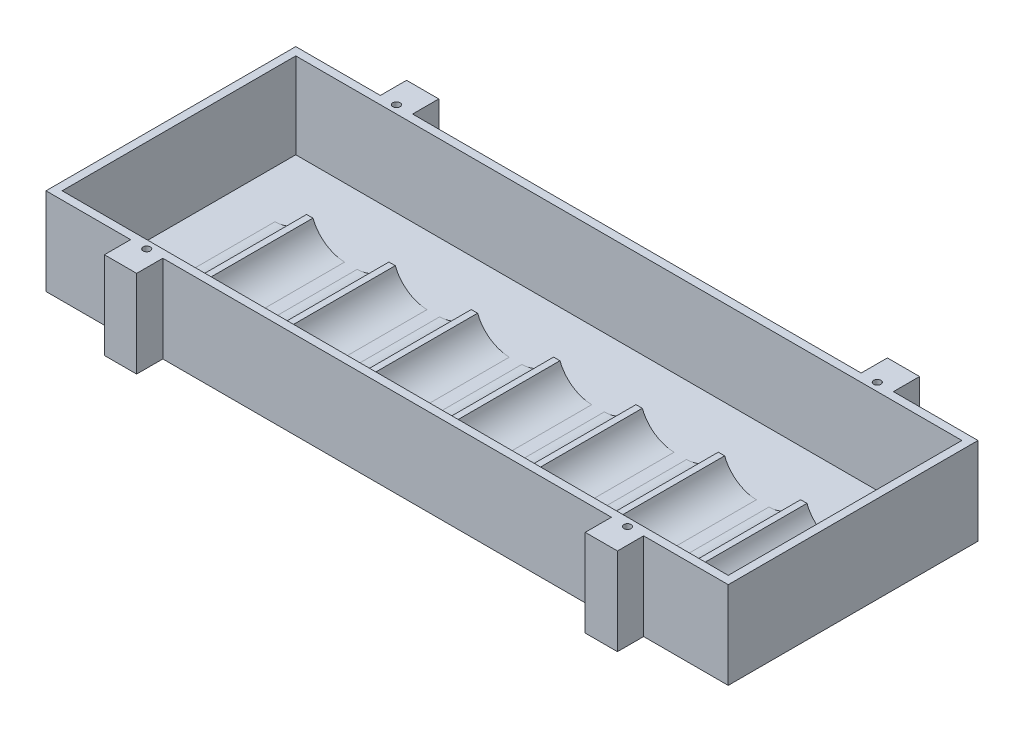
SolidWorks part; units mm, degrees
material "ABS"
ref_plane "Front Plane" through (0, 0, 0) normal (0, 0, 1) x (1, 0, 0)
ref_plane "Top Plane" through (0, 0, 0) normal (0, 1, 0) x (1, 0, 0)
ref_plane "Right Plane" through (0, 0, 0) normal (1, 0, 0) x (0, 0, -1)
sketch "Sketch1" plane through (0, 0, 0) normal (0, 1, 0) x (1, 0, 0)
  line L0 (2.54, -2.54) -> (2.54, -76.2)
  line L1 (0, 0) -> (215.08, 0)
  line L2 (0, 0) -> (0, -78.74)
  line L3 (0, -78.74) -> (215.08, -78.74)
  line L4 (215.08, 0) -> (215.08, -78.74)
  line L5 (2.54, -76.2) -> (212.54, -76.2)
  line L6 (212.54, -2.54) -> (212.54, -76.2)
  line L7 (2.54, -2.54) -> (212.54, -2.54)
  line L8 (0, 0) -> (0, 8.255)
  line L9 (0, 8.255) -> (215.08, 8.255)
  line L10 (215.08, 8.255) -> (215.08, 0)
  line L11 (0, -78.74) -> (0, -86.995)
  line L12 (0, -86.995) -> (215.08, -86.995)
  line L13 (215.08, -86.995) -> (215.08, -78.74)
  dimension "D1" = 73.66
  dimension "D2" = 210
  dimension "D4" = 10.795
  dimension "D5" = 95.25
  dimension "D3" = 2.54
extrude "Boss-Extrude1" add sketch "Sketch1" against normal blind 0.508 contours L2 L3 L4 L1
extrude "Boss-Extrude2" add sketch "Sketch1<3>" along normal blind 27 contours L10 L9 L8 L1 | L12 L13 L3 L11 | L4 L1 L2 L3 L0 L7 L6 L5 region at (107.54, 0, -4.1275) region at (107.54, 0, 2.2904) region at (107.54, 0, 82.8675)
sketch "Sketch1<3>" plane through (0, 0, 0) normal (0, 1, 0) x (1, 0, 0) same geometry as "Sketch1"
sketch "Sketch2" plane through (0, 0, 0) normal (0, 1, 0) x (-1, 0, 0)
  line L0 (-28.54, 0) -> (-28.54, 78.74) construction
  line L1 (-2.54, 2.54) -> (-2.54, 76.2) construction
  line L2 (-17.54, 0) -> (-17.54, 78.74) construction
  line L9 (0, 0) -> (-215.08, 0) construction
  line L10 (0, 78.74) -> (-215.08, 78.74) construction
  dimension "D1" = 26
  dimension "D2" = 15
sketch "Sketch5" plane through (0, 0, 2.54) normal (0, 0, 1) x (1, 0, 0)
  line L0 (28.54, 0) -> (28.54, 7) construction
  line L1 (29.54, 7) -> (27.54, 7)
  line L2 (0, 0) -> (215.08, 0) construction
  line L3 (17.54, 0) -> (39.54, 0)
  line L4 (55.4988, 7) -> (53.4988, 7)
  line L5 (43.4988, 0) -> (65.4988, 0)
  line L6 (54.4988, 0) -> (54.4988, 7) construction
  line L7 (81.4576, 7) -> (79.4576, 7)
  line L8 (69.4576, 0) -> (91.4576, 0)
  line L9 (80.4576, 0) -> (80.4576, 7) construction
  line L10 (107.4164, 7) -> (105.4164, 7)
  line L11 (95.4164, 0) -> (117.4164, 0)
  line L12 (106.4164, 0) -> (106.4164, 7) construction
  line L13 (133.3752, 7) -> (131.3752, 7)
  line L14 (121.3752, 0) -> (143.3752, 0)
  line L15 (132.3752, 0) -> (132.3752, 7) construction
  line L31 (159.334, 7) -> (157.334, 7)
  line L32 (147.334, 0) -> (169.334, 0)
  line L33 (158.334, 0) -> (158.334, 7) construction
  line L34 (185.2928, 7) -> (183.2928, 7)
  line L35 (173.2928, 0) -> (195.2928, 0)
  line L36 (184.2928, 0) -> (184.2928, 7) construction
  line L37 (170.06, 7) -> (168.06, 7) [skipped]
  line L38 (158.06, 0) -> (180.06, 0) [skipped]
  line L39 (169.06, 0) -> (169.06, 7) construction
  line L40 (145.64, 0) -> (145.64, 7) construction
  line L41 (134.64, 0) -> (156.64, 0) [skipped]
  line L42 (146.64, 7) -> (144.64, 7) [skipped]
  line L43 (122.22, 0) -> (122.22, 7) construction
  line L44 (111.22, 0) -> (133.22, 0) [skipped]
  line L45 (123.22, 7) -> (121.22, 7) [skipped]
  line L46 (98.8, 0) -> (98.8, 7) construction
  line L47 (87.8, 0) -> (109.8, 0) [skipped]
  line L48 (99.8, 7) -> (97.8, 7) [skipped]
  line L49 (75.38, 0) -> (75.38, 7) construction
  line L50 (64.38, 0) -> (86.38, 0) [skipped]
  line L51 (76.38, 7) -> (74.38, 7) [skipped]
  line L52 (51.96, 0) -> (51.96, 7) construction
  line L53 (40.96, 0) -> (62.96, 0) [skipped]
  line L54 (52.96, 7) -> (50.96, 7) [skipped]
  arc A0 (17.54, 0) -> (27.54, 7) centre (17.292, 10.9972) ccw
  arc A1 (39.54, 0) -> (29.54, 7) centre (39.788, 10.9972) cw
  arc A2 (65.4988, 0) -> (55.4988, 7) centre (65.7468, 10.9972) cw
  arc A3 (43.4988, 0) -> (53.4988, 7) centre (43.2508, 10.9972) ccw
  arc A4 (91.4576, 0) -> (81.4576, 7) centre (91.7056, 10.9972) cw
  arc A5 (69.4576, 0) -> (79.4576, 7) centre (69.2096, 10.9972) ccw
  arc A6 (117.4164, 0) -> (107.4164, 7) centre (117.6644, 10.9972) cw
  arc A7 (95.4164, 0) -> (105.4164, 7) centre (95.1684, 10.9972) ccw
  arc A8 (143.3752, 0) -> (133.3752, 7) centre (143.6232, 10.9972) cw
  arc A9 (121.3752, 0) -> (131.3752, 7) centre (121.1272, 10.9972) ccw
  arc A20 (169.334, 0) -> (159.334, 7) centre (169.582, 10.9972) cw
  arc A21 (147.334, 0) -> (157.334, 7) centre (147.086, 10.9972) ccw
  arc A22 (195.2928, 0) -> (185.2928, 7) centre (195.5408, 10.9972) cw
  arc A23 (173.2928, 0) -> (183.2928, 7) centre (173.0448, 10.9972) ccw
  arc A24 (180.06, 0) -> (170.06, 7) centre (180.308, 10.9972) cw [skipped]
  arc A25 (158.06, 0) -> (168.06, 7) centre (157.812, 10.9972) ccw [skipped]
  arc A26 (134.64, 0) -> (144.64, 7) centre (134.392, 10.9972) ccw [skipped]
  arc A27 (156.64, 0) -> (146.64, 7) centre (156.888, 10.9972) cw [skipped]
  arc A28 (111.22, 0) -> (121.22, 7) centre (110.972, 10.9972) ccw [skipped]
  arc A29 (133.22, 0) -> (123.22, 7) centre (133.468, 10.9972) cw [skipped]
  arc A30 (87.8, 0) -> (97.8, 7) centre (87.552, 10.9972) ccw [skipped]
  arc A31 (109.8, 0) -> (99.8, 7) centre (110.048, 10.9972) cw [skipped]
  arc A32 (64.38, 0) -> (74.38, 7) centre (64.132, 10.9972) ccw [skipped]
  arc A33 (86.38, 0) -> (76.38, 7) centre (86.628, 10.9972) cw [skipped]
  arc A34 (62.96, 0) -> (52.96, 7) centre (63.208, 10.9972) cw [skipped]
  arc A35 (40.96, 0) -> (50.96, 7) centre (40.712, 10.9972) ccw [skipped]
  dimension "D2" = 11
  dimension "D1" = 1
  dimension "D3" = 7
  dimension "D6" = 25.9588
  dimension "D4" = 6
  dimension "D5" = 7
extrude "Boss-Extrude3" add sketch "Sketch5" along normal blind 32.5 from offset 21.59
extrude "Boss-Extrude4" add sketch "Sketch1<4>" against normal up to surface (0.508 mm away) contours L10 L9 L8 L1 | L12 L13 L3 L11 region at (107.54, 0, -4.1275) region at (107.54, 0, 82.8675) up to face at (107.54, -0.508, 39.37)
sketch "Sketch1<4>" plane through (0, 0, 0) normal (0, 1, 0) x (1, 0, 0) same geometry as "Sketch1"
sketch "Sketch6" plane through (0, 27, 0) normal (0, 1, 0) x (1, 0, 0)
  line L0 (0, 0) -> (215.08, 0) construction
  line L1 (215.08, 8.255) -> (215.08, -86.995) construction
  line L2 (0, -86.995) -> (0, 8.255) construction
  line L3 (0, -39.37) -> (14.6137, -39.37) construction
  point P5 (31.75, 0)
  point P6 (183.33, 0)
  point P9 (183.33, -78.74)
  point P10 (31.75, -78.74)
  dimension "D1" = 31.75
  dimension "D2" = 31.75
hole_wizard "#4-40 Tapped Hole2" positions "Sketch10" profile "Sketch9" tap size "#4-40" standard "Ansi Inch"
sketch "Sketch10" plane through (0, 27, 0) normal (0, 1, 0) x (-1, 0, 0)
  point P0 (-31.75, 0)
  point P1 (-183.33, 0)
  point P8 (-31.75, 78.74)
  point P11 (-183.33, 78.74)
sketch "Sketch9" plane through (31.75, 27, 0) normal (1, 0, 0) x (0, 0, 1)
  line L0 (0, 0) -> (0, 8.2992)
  line L1 (0, 8.2992) -> (1.1303, 7.62)
  line L2 (1.1303, 7.62) -> (1.1303, 0)
  line L5 (1.1303, 0) -> (0, 0)
  line L10 (0, 8.2992) -> (-1.1303, 7.62) construction
  line L11 (0, -6.35) -> (0, 107.95) construction
  dimension "Tap Drill Dia." = 2.2606
  dimension "Tap Drill Depth" = 7.62
  dimension "Drill Angle" = 118
cosmetic thread "Hole Thread2" parameters "D1"=5.588, "D2"=2.8448
cosmetic thread "Hole Thread3" parameters "D1"=5.588, "D2"=2.8448
cosmetic thread "Hole Thread4" parameters "D1"=5.588, "D2"=2.8448
cosmetic thread "Hole Thread5" parameters "D1"=5.588, "D2"=2.8448
sketch "Sketch12" plane through (0, 27, 0) normal (0, 1, 0) x (1, 0, 0)
  line L0 (107.54, 8.255) -> (107.54, -86.995) construction
  line L1 (0, 8.255) -> (215.08, 8.255) construction
  line L2 (0, -86.995) -> (215.08, -86.995) construction
sketch "Sketch13" plane through (0, 27, 0) normal (0, 1, 0) x (1, 0, 0)
  line L0 (0, 8.255) -> (215.08, 8.255) construction
  line L1 (36.83, 8.255) -> (178.25, 8.255)
  line L2 (36.83, 8.255) -> (36.83, 0)
  line L3 (36.83, 0) -> (178.25, 0)
  line L4 (178.25, 8.255) -> (178.25, 0)
  line L5 (2.54, -2.54) -> (212.54, -2.54) construction
  line L6 (0, -39.37) -> (14.211, -39.37) construction
  line L7 (0, -86.995) -> (0, 8.255) construction
  line L8 (178.25, -86.995) -> (178.25, -78.74)
  line L9 (36.83, -78.74) -> (178.25, -78.74)
  line L10 (36.83, -86.995) -> (178.25, -86.995)
  line L11 (36.83, -86.995) -> (36.83, -78.74)
  line L12 (2.54, -2.54) -> (212.54, -2.54) construction
  line L13 (0, 8.255) -> (26.67, 8.255)
  line L14 (0, 8.255) -> (0, 0)
  line L15 (0, 0) -> (26.67, 0)
  line L16 (26.67, 8.255) -> (26.67, 0)
  line L17 (107.54, 8.255) -> (107.54, -13.155) construction
  line L18 (188.41, 8.255) -> (188.41, 0)
  line L19 (215.08, 0) -> (188.41, 0)
  line L20 (215.08, 8.255) -> (215.08, 0)
  line L21 (215.08, 8.255) -> (188.41, 8.255)
  line L22 (188.41, -86.995) -> (188.41, -78.74)
  line L23 (215.08, -78.74) -> (188.41, -78.74)
  line L24 (215.08, -86.995) -> (188.41, -86.995)
  line L25 (215.08, -86.995) -> (215.08, -78.74)
  line L26 (26.67, -86.995) -> (26.67, -78.74)
  line L27 (0, -78.74) -> (26.67, -78.74)
  line L28 (0, -86.995) -> (0, -78.74)
  line L29 (0, -86.995) -> (26.67, -86.995)
  dimension "D1" = 5.08
  dimension "D2" = 5.08
  dimension "D3" = 2.54
  dimension "D4" = 2.54
  dimension "D5" = 5.08
extrude "Cut-Extrude1" cut sketch "Sketch13" against normal through all
